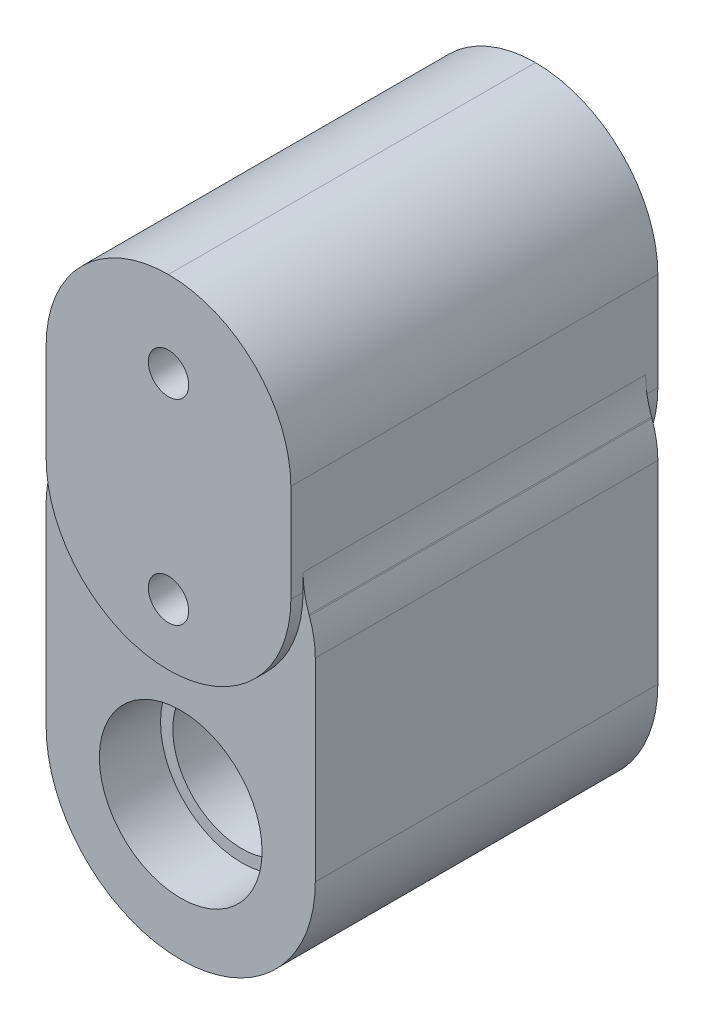
SolidWorks part; units mm, degrees
ref_plane "Спереди" through (0, 0, 0) normal (0, 0, 1) x (1, 0, 0)
ref_plane "Сверху" through (0, 0, 0) normal (0, 1, 0) x (1, 0, 0)
ref_plane "Справа" through (0, 0, 0) normal (1, 0, 0) x (0, 0, -1)
sketch "Эскиз1" plane through (0, 0, 0) normal (0, 0, 1) x (1, 0, 0)
  line L0 (0, 36) -> (0, -11) construction
  line L1 (-11, 38) -> (11, 38)
  line L2 (-11, 38) -> (-11, -11)
  line L3 (-11, -11) -> (11, -11)
  line L4 (11, 38) -> (11, -11)
  line L6 (-11, 0) -> (11, 0) construction
  point P0 (11, 36.5275)
  dimension "D2" = 11
  dimension "D3" = 38
  dimension "D5" = 22
extrude "тело" add sketch "Эскиз1" along normal blind 14 and the other way blind 14
sketch "Эскиз2" plane through (0, 0, 14) normal (0, 0, 1) x (1, 0, 0)
  circle A0 centre (0, 0) radius 6.65
  dimension "D1" = 13.3
extrude "углубление для подшипника" cut sketch "Эскиз2" against normal blind 5
sketch "Эскиз4" plane through (0, 0, 9) normal (0, 0, 1) x (1, 0, 0)
  line L1 (0, 36) -> (0, -11) construction
  line L2 (-11, 0) -> (11, 0) construction
  circle A0 centre (0, 0) radius 5.65
  circle A1 centre (0, 0) radius 6.65 construction
  dimension "D1" = 1
extrude "сквозное отверстие" cut sketch "Эскиз4" against normal through all
mirror "Зеркальное отражение2" about plane through (0, 0, 0) normal (0, 0, 1) of "углубление для подшипника"
fillet "Скругление1" radius 11 2 edges at (11, -11, 0) (-11, -11, 0)
sketch "Эскиз5" plane through (0, 0, -14) normal (0, 0, -1) x (-1, 0, 0)
  line L0 (0, 38) -> (0, -11) construction
  line L1 (-11, 38) -> (11, 38) construction
  circle A0 centre (0, 31) radius 1.65
  circle A1 centre (0, 15) radius 1.65
  circle A2 centre (0, 0) radius 6.65 construction
  point P4 (0, -11)
  dimension "D1" = 3.3
  dimension "D2" = 16
  dimension "D3" = 15
extrude "отверстия под болты" cut sketch "Эскиз5" against normal through all
sketch "Эскиз9" plane through (0, 0, 14) normal (0, 0, 1) x (1, 0, 0)
  line L1 (-11, 10) -> (11, 10) construction
  line L2 (-10, 38) -> (10, 38)
  line L4 (-11, 38) -> (-11, 0) construction
  line L5 (11, 0) -> (11, 38) construction
  line L6 (-10, 20) -> (-10, 38)
  line L9 (10, 38) -> (10, 20)
  line L10 (11, 38) -> (-11, 38) construction
  arc A0 (-10, 20) -> (10, 20) centre (0, 20) ccw
  circle A1 centre (0, 15) radius 1.65
  circle A2 centre (0, 31) radius 1.65
  circle A3 centre (0, 31) radius 1.65 construction
  circle A5 centre (0, 15) radius 1.65 construction
  point P4 (10, 36)
  point P20 (9.709, 22.3949)
  point P23 (0, 38)
  dimension "D1" = 10
  dimension "D2" = 5
  dimension "D3" = 20
extrude "выступы" add sketch "Эскиз9" along normal blind 1
mirror "Зеркальное отражение1" about plane through (0, 0, 0) normal (0, 0, 1) of "выступы"
sketch "Эскиз10" plane through (0, 0, 14) normal (0, 0, 1) x (1, 0, 0)
  line L0 (-10, 38) -> (-11, 38)
  line L1 (-11, 38) -> (-11, 17.2525)
  line L2 (-11, 38) -> (-11, 0) construction
  line L3 (0, 38) -> (0, 15) construction
  line L4 (-10, 38) -> (-10, 20)
  line L5 (-11, 17.2525) -> (-10, 20)
  line L6 (10, 38) -> (-10, 38) construction
  line L7 (11, 17.2525) -> (10, 20)
  line L8 (10, 38) -> (10, 20)
  line L9 (11, 38) -> (11, 17.2525)
  line L10 (10, 38) -> (11, 38)
  point P15 (0, 0)
  dimension "D1" = 20
extrude "Сглаживание перехода" cut sketch "Эскиз10" against normal up to next
fillet "Скругление2" radius 8 4 edges at (10, 20, 0) (11, 17.2525, 0) (-10, 20, 0) (-11, 17.2525, 0)
fillet "Скругление3" radius 10 2 edges at (-10, 38, 0) (10, 38, 0)
